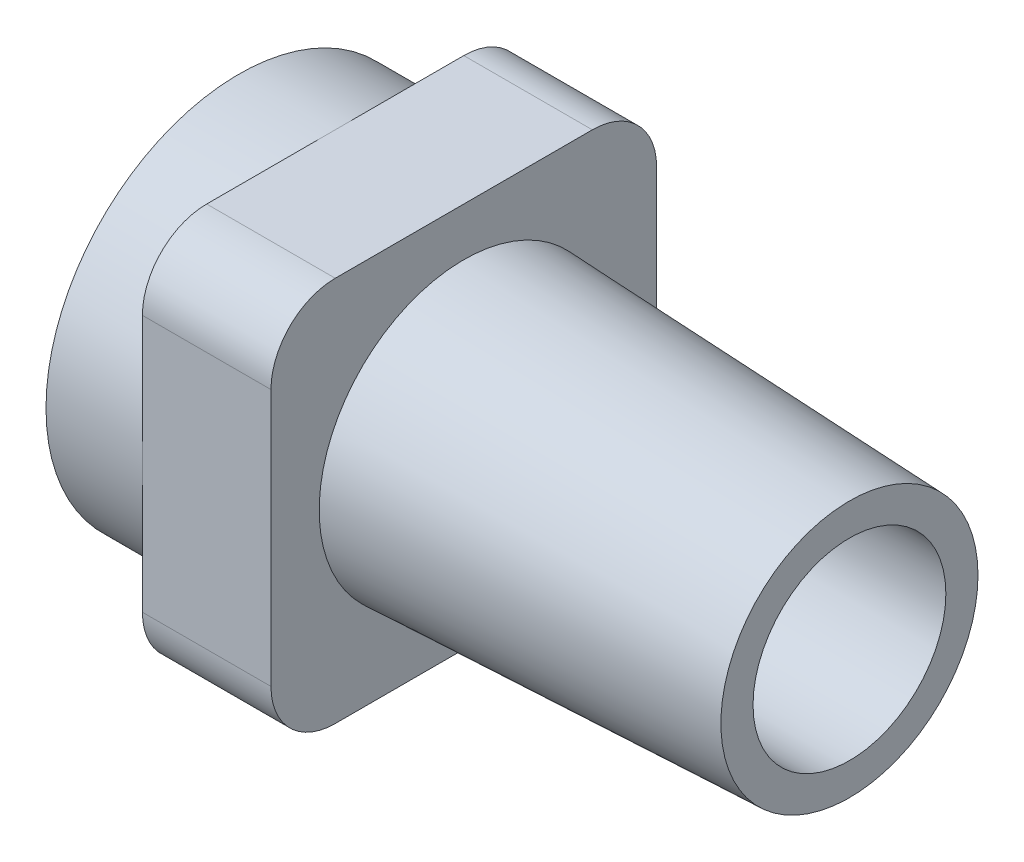
SolidWorks part; units mm, degrees
material "Silicon Rubber"
ref_plane "Front Plane" through (0, 0, 0) normal (0, 0, 1) x (1, 0, 0)
ref_plane "Top Plane" through (0, 0, 0) normal (0, 1, 0) x (1, 0, 0)
ref_plane "Right Plane" through (0, 0, 0) normal (1, 0, 0) x (0, 0, -1)
ref_axis "CentralAxis" through (-4.025, 0, 0) along (1, 0, 0)
sketch "BaseS" plane through (0, 0, 0) normal (1, 0, 0) x (0, 0, -1)
  line L1 (-3, 3) -> (3, 3)
  line L2 (-3, 3) -> (-3, -3)
  line L3 (-3, -3) -> (3, -3)
  line L4 (3, 3) -> (3, -3)
  line L5 (-3, 3) -> (3, -3) construction
  line L6 (-3, -3) -> (3, 3) construction
  point P0 (0, 0)
  dimension "Dim" = 6
extrude "Base" add sketch "BaseS" along normal mid plane 2
sketch "InsideWireHoldingBodyS" plane through (-1, 0, 0) normal (-1, 0, 0) x (0, 0, 1)
  line L0 (-3, 3) -> (3, 3) construction
  circle A0 centre (0, 0) radius 3
extrude "InsideWireHoldingBody" add sketch "InsideWireHoldingBodyS" along normal blind 1.5
ref_plane "RearEndLoftPlane" through (7, 0, 0) normal (1, 0, 0) x (0, 0, -1)
sketch "FrontFaceS" plane through (1, 0, 0) normal (1, 0, 0) x (0, 0, -1)
  circle A0 centre (0, 0) radius 2.25
  dimension "Diameter" = 4.5
sketch "RearFaceS" plane through (7, 0, 0) normal (1, 0, 0) x (0, 0, -1)
  circle A0 centre (0, 0) radius 2
  circle A1 centre (0, 0) radius 2.25 construction
  dimension "RefDiameter" = 4
  dimension "DiaControl" = 0.25
loft "StrainReliefBody" add profiles "FrontFaceS", "RearFaceS" connector at (1, 0, -2.25) connector at (7, 0, -2)
sketch "HoleS" plane through (0, 0, 0) normal (1, 0, 0) x (0, 0, -1)
  circle A0 centre (0, 0) radius 1.5
  dimension "Diameter" = 3
extrude "Hole" cut sketch "HoleS" against normal through all both and the other way through all
fillet "BaseFillet" radius 1 4 edges at (0, -3, 3) (0, -3, -3) (0, 3, -3) (0, 3, 3)
